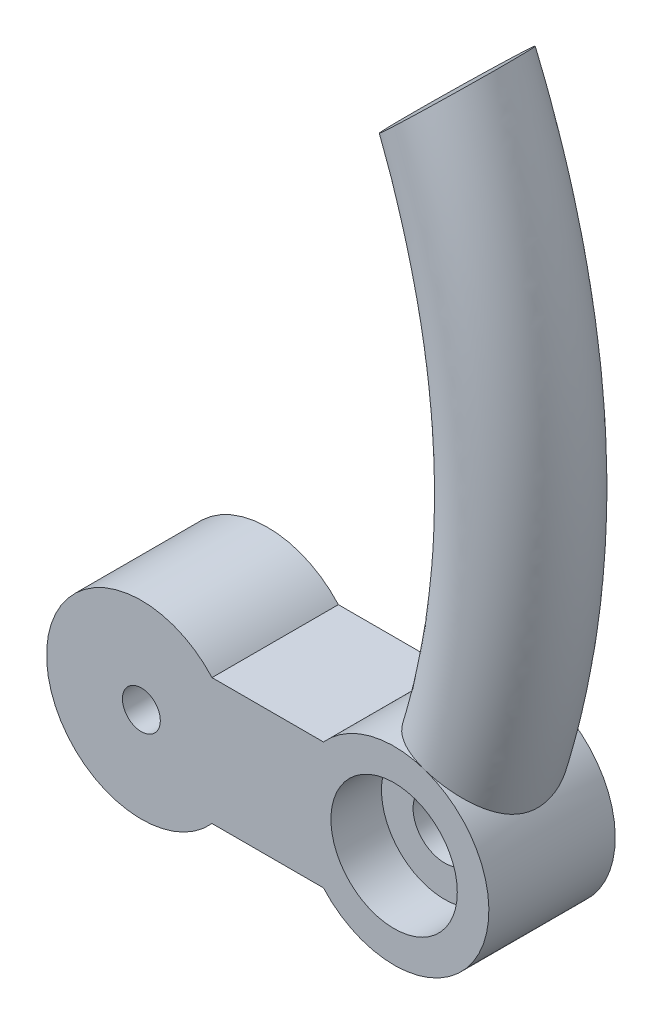
SolidWorks part; units mm, degrees
ref_plane "Front Plane" through (0, 0, 0) normal (0, 0, 1) x (1, 0, 0)
ref_plane "Top Plane" through (0, 0, 0) normal (0, 1, 0) x (1, 0, 0)
ref_plane "Right Plane" through (0, 0, 0) normal (1, 0, 0) x (0, 0, -1)
sketch "Sketch1" plane through (0, 0, 0) normal (0, 0, 1) x (1, 0, 0)
  line L1 (4.4098, -5) -> (-4.4098, -5)
  line L3 (4.4098, 5) -> (-4.4098, 5)
  line L5 (2.6148, -1.3074) -> (0, 0) construction
  arc A0 (-2.6148, -1.3074) -> (-2.6148, 1.3074) centre (-10, 0) ccw
  arc A1 (4.4098, -5) -> (4.4098, 5) centre (10, 0) ccw
  circle A2 centre (-10, 0) radius 1.5
  circle A3 centre (10, 0) radius 2.5
  arc A4 (-4.4098, 5) -> (-4.4098, -5) centre (-10, 0) ccw
  point P0 (0, 0)
  dimension "D3" = 15
  dimension "D4" = 15
  dimension "D5" = 3
  dimension "D6" = 5
extrude "Boss-Extrude1" add sketch "Sketch1" along normal mid plane 10 contours L3 A4 L1 A1 A2 A3 region at (-0.3233, 0, 0)
sketch "Sketch3" plane through (0, 0, -5) normal (0, 0, -1) x (-1, 0, 0)
  circle A0 centre (10, 0) radius 5
  dimension "D1" = 10
extrude "Cut-Extrude2" cut sketch "Sketch3" against normal blind 4
sketch "Sketch5" plane through (0, 0, 0) normal (0, 1, 0) x (1, 0, 0)
  circle A0 centre (10, 0) radius 5
  dimension "D1" = 10
sketch "Sketch4" plane through (0, 0, 0) normal (0, 0, 1) x (1, 0, 0)
  line L0 (10, 0) -> (10, 50) construction
  line L1 (10, 25) -> (20, 25) construction
  line L2 (10, 0) -> (20, 25) construction
  line L3 (20, 25) -> (10, 50) construction
  line L6 (4.4098, 5) -> (-4.4098, 5)
  line L7 (-4.4098, -5) -> (4.4098, -5)
  line L8 (4.4098, 5) -> (3.8788, 5)
  line L9 (-4.4098, -5) -> (4.4098, -5)
  arc A2 (-4.4098, 5) -> (-4.4098, -5) centre (-10, 0) ccw
  arc A3 (4.4098, -5) -> (4.4098, 5) centre (10, 0) ccw
  arc A5 (12.7854, 6.9636) -> (12.4349, 7.0937) centre (10, 0) ccw
  spline S0 degree 2 poles (10, 0) (20, 25) (10, 50) knots 0 0 0 1 1 1
  point P7 (3.0364, 57.2146)
  dimension "D1" = 50
  dimension "D2" = 10
  dimension "D6" = 0
sweep "Sweep1" add profiles "Sketch5" path "Sketch4"
sketch "Sketch2" plane through (0, 0, 5) normal (0, 0, 1) x (1, 0, 0)
  circle A0 centre (10, 0) radius 5
  dimension "D1" = 10
extrude "Cut-Extrude1" cut sketch "Sketch2" against normal blind 4
sketch "Sketch6" plane through (0, 0, -5) normal (0, 0, -1) x (-1, 0, 0)
  line L0 (-12.5, 0) -> (-7.5, 0) construction
  circle A0 centre (-10, 0) radius 2.5
extrude "Cut-Extrude3" cut sketch "Sketch6" against normal blind 10
